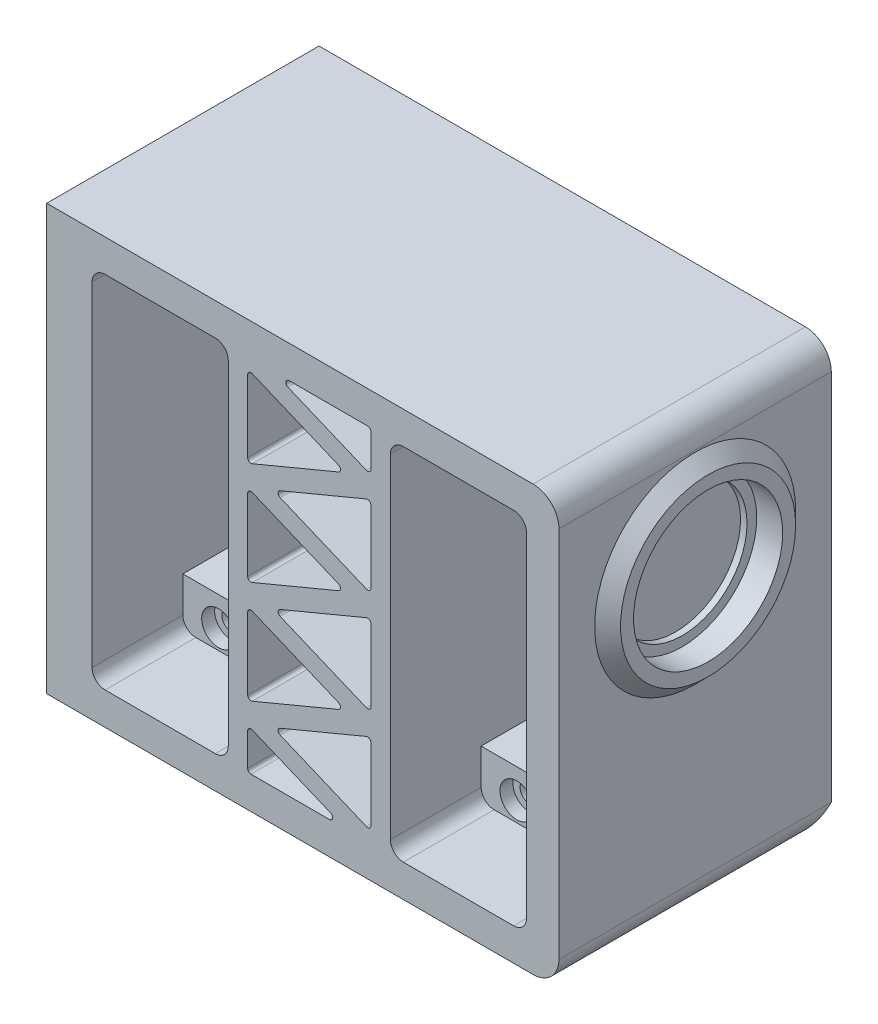
SolidWorks part; units mm, degrees
ref_plane "Front Plane" through (0, 0, 0) normal (0, 0, 1) x (1, 0, 0)
ref_plane "Top Plane" through (0, 0, 0) normal (0, 1, 0) x (1, 0, 0)
ref_plane "Right Plane" through (0, 0, 0) normal (1, 0, 0) x (0, 0, -1)
sketch "Sketch1" plane through (0, 0, 0) normal (0, 0, 1) x (1, 0, 0)
  line L0 (5, 60.5) -> (26, 60.5)
  line L1 (0, 0) -> (77, 0)
  line L2 (0, 0) -> (0, 65.5)
  line L3 (0, 65.5) -> (77, 65.5)
  line L4 (77, 0) -> (77, 65.5)
  line L5 (51, 60.5) -> (72, 60.5)
  line L6 (51, 60.5) -> (51, 5)
  line L7 (51, 5) -> (72, 5)
  line L8 (72, 60.5) -> (72, 5)
  line L9 (5, 60.5) -> (5, 5)
  line L10 (5, 5) -> (26, 5)
  line L12 (26, 60.5) -> (26, 5)
  line L13 (5, 53) -> (26, 53)
  line L14 (51, 53) -> (72, 53)
  line L15 (5, 12.5) -> (26, 12.5)
  line L16 (51, 12.5) -> (72, 12.5)
  line L17 (10.5, 57.5) -> (20.5, 57.5) construction
  line L18 (10.5, 8) -> (20.5, 8) construction
  line L19 (15.5, 57.5) -> (15.5, 8) construction
  line L20 (5, 32.75) -> (26, 32.75) construction
  line L21 (51, 32.75) -> (72, 32.75) construction
  line L22 (61.5, 57.5) -> (61.5, 8) construction
  line L23 (56.5, 57.5) -> (66.5, 57.5) construction
  line L24 (56.5, 8) -> (66.5, 8) construction
  circle A0 centre (10.5, 57.5) radius 1.5
  circle A1 centre (20.5, 57.5) radius 1.5
  circle A2 centre (10.5, 8) radius 1.5
  circle A3 centre (20.5, 8) radius 1.5
  circle A4 centre (56.5, 57.5) radius 1.5
  circle A5 centre (66.5, 57.5) radius 1.5
  circle A6 centre (66.5, 8) radius 1.5
  circle A7 centre (56.5, 8) radius 1.5
  point P33 (15.5, 32.75)
  point P34 (15.5, 32.75)
  point P41 (61.5, 32.75)
  point P42 (61.5, 32.75)
  point P53 (61.5, 8)
  point P55 (61.5, 57.5)
  dimension "D13" = 3
  dimension "D1" = 21
  dimension "D2" = 5
  dimension "D3" = 55.5
  dimension "D4" = 55.5
  dimension "D5" = 21
  dimension "D6" = 5
  dimension "D7" = 5
  dimension "D8" = 25
  dimension "D9" = 5
  dimension "D10" = 7.5
  dimension "D11" = 7.5
  dimension "D12" = 10
  dimension "D15" = 49.5
extrude "Boss-Extrude2" add sketch "Sketch1" against normal blind 28 contours L1 L4 L3 L2 L5 L8 L7 L6 L0 L12 L10 L9 | L9 L13 L12 L0 | L15 L9 L10 L12 | L16 L6 L7 L8 | L6 L14 L8 L5 | A0 | A1 | A4 | A5 | A6 | A7 | A3 | A2 region at (15.5, 56.676, 0) region at (15.5, 8.824, 0) region at (38.5, 32.75, 0) region at (61.5, 56.676, 0) region at (61.5, 8.824, 0) region at (10.5, 57.5, 0) region at (20.5, 57.5, 0) region at (56.5, 57.5, 0) region at (66.5, 57.5, 0) region at (66.5, 8, 0) region at (56.5, 8, 0)
extrude "Boss-Extrude4" add sketch "Sketch1<4>" along normal blind 14 contours L1 L4 L3 L2 L5 L8 L7 L6 L0 L12 L10 L9 region at (38.5, 32.75, 0)
sketch "Sketch1<4>" plane through (0, 0, 0) normal (0, 0, 1) x (1, 0, 0) same geometry as "Sketch1"
extrude "Cut-Extrude1" cut sketch "Sketch1<5>" against normal blind 12 contours A0 | A2 | A3 | A7 | A6 | A4 | A1 | A5 region at (10.5, 57.5, 0) region at (10.5, 8, 0) region at (20.5, 8, 0) region at (56.5, 57.5, 0) region at (66.5, 8, 0) region at (56.5, 8, 0)
sketch "Sketch1<5>" plane through (0, 0, 0) normal (0, 0, 1) x (1, 0, 0) same geometry as "Sketch1"
sketch "Sketch5" plane through (0, 0, 14) normal (0, 0, 1) x (1, 0, 0)
  line L0 (28.4223, 59.1157) -> (44.105, 52.5714)
  line L1 (26, 5) -> (51, 5)
  line L2 (26, 5) -> (26, 60.5)
  line L3 (26, 60.5) -> (51, 60.5)
  line L4 (51, 5) -> (51, 60.5)
  line L5 (26, 60.5) -> (26, 5) construction
  line L6 (51, 60.5) -> (51, 5) construction
  line L7 (5, 60.5) -> (26, 60.5) construction
  line L8 (5, 5) -> (26, 5) construction
  line L9 (29, 60.5) -> (48, 60.5)
  line L10 (48, 5) -> (48, 60.5)
  line L11 (29, 5) -> (48, 5)
  line L12 (29, 5) -> (29, 60.5)
  line L13 (29, 60.5) -> (48, 52.5714)
  line L14 (48, 52.5714) -> (29, 44.6429)
  line L15 (29, 44.6429) -> (48, 36.7143)
  line L16 (48, 36.7143) -> (29, 28.7857)
  line L17 (29, 28.7857) -> (48, 20.8571)
  line L18 (48, 20.8571) -> (29, 12.9286)
  line L19 (29, 12.9286) -> (48, 5)
  line L20 (44.105, 52.5714) -> (25.105, 44.6429)
  line L21 (25.105, 44.6429) -> (44.105, 36.7143)
  line L22 (44.105, 36.7143) -> (25.105, 28.7857)
  line L23 (25.105, 28.7857) -> (44.105, 20.8571)
  line L24 (44.105, 20.8571) -> (25.105, 12.9286)
  line L25 (25.105, 12.9286) -> (47.4223, 3.6157)
  line L26 (29.5777, 61.8843) -> (51.895, 52.5714)
  line L27 (51.895, 52.5714) -> (32.895, 44.6429)
  line L28 (32.895, 44.6429) -> (51.895, 36.7143)
  line L29 (51.895, 36.7143) -> (32.895, 28.7857)
  line L30 (32.895, 28.7857) -> (51.895, 20.8571)
  line L31 (51.895, 20.8571) -> (32.895, 12.9286)
  line L32 (32.895, 12.9286) -> (48.5777, 6.3843)
  dimension "D2" = 1.5
  dimension "D1" = 3
  dimension "D4" = 3
  dimension "D3" = 1.5
extrude "Cut-Extrude2" cut sketch "Sketch5" against normal through all contours L20 L0 L12 | L9 L26 L10 | L27 L28 L10 | L22 L21 L12 | L29 L30 L10 | L24 L23 L12 | L31 L32 L10 | L25 L12 L11 region at (34.035, 52.5714, 14) region at (42.965, 58.3989, 14) region at (34.035, 36.7143, 14) region at (42.965, 44.6429, 14) region at (42.965, 28.7857, 14) region at (34.035, 20.8571, 14) region at (42.965, 12.9286, 14) region at (34.035, 7.1011, 14)
fillet "Fillet4" radius 0.5 24 edges at (44.105, 5, -7) (29, 11.3032, -7) (29, 5, -7) (48, 6.6254, -7) (48, 19.2318, -7) (32.895, 12.9286, -7) (29, 14.5539, -7) (29, 27.1604, -7) (44.105, 20.8571, -7) (48, 22.4825, -7) (48, 35.0889, -7) (32.895, 28.7857, -7) (44.105, 36.7143, -7) (29, 30.4111, -7) (29, 43.0175, -7) (48, 38.3396, -7) (32.895, 44.6429, -7) (48, 50.9461, -7) (29, 46.2682, -7) (44.105, 52.5714, -7) (29, 58.8746, -7) (48, 54.1968, -7) (48, 60.5, -7) (32.895, 60.5, -7)
sketch "Sketch8" plane through (0, 12.5, 0) normal (0, 1, 0) x (1, 0, 0)
  line L0 (26, 28) -> (26, 0) construction
  line L1 (5, 28) -> (26, 28)
  line L2 (5, 28) -> (5, 8)
  line L3 (5, 8) -> (26, 8)
  line L4 (26, 28) -> (26, 8)
  line L5 (51, 0) -> (72, 0) construction
  line L6 (51, 28) -> (72, 28)
  line L7 (51, 28) -> (51, 8)
  line L8 (51, 8) -> (72, 8)
  line L9 (72, 28) -> (72, 8)
  line L10 (72, 28) -> (72, 0) construction
  dimension "D1" = 8
extrude "Cut-Extrude8" cut sketch "Sketch8" against normal blind 10
ref_plane "Midplane" through (0, 32.75, 0) normal (0, 1, 0) x (1, 0, 0)
ref_plane "Plane2" through (61.5, 0, 0) normal (1, 0, 0) x (0, 0, -1)
ref_plane "Plane3" through (15.5, 0, 0) normal (1, 0, 0) x (0, 0, -1)
sketch "Sketch10" plane through (61.5, 0, 0) normal (1, 0, 0) x (0, 0, -1)
  line L0 (28, 2.5) -> (8, 2.5) construction
  line L1 (8, 2.5) -> (8, 12.5) construction
  line L2 (28, 2.5) -> (8, 2.5)
  line L3 (8, 2.5) -> (8, 12.5)
  line L4 (8, 12.5) -> (18, 2.5)
  dimension "D1" = 45
extrude "Boss-Extrude5" add sketch "Sketch10" along normal blind 1.5 and the other way blind 1.5 contours L4 L3 L2 region at (61.5, 5.8333, -11.3333)
sketch "Sketch11" plane through (15.5, 0, 0) normal (1, 0, 0) x (0, 0, -1)
  line L0 (28, 2.5) -> (8, 2.5) construction
  line L1 (8, 2.5) -> (8, 12.5) construction
  line L2 (28, 2.5) -> (8, 2.5)
  line L3 (8, 2.5) -> (8, 12.5)
  line L4 (8, 12.5) -> (18, 2.5)
  dimension "D1" = 45
extrude "Boss-Extrude6" add sketch "Sketch11" along normal blind 1.5 and the other way blind 1.5 contours L4 L3 L2 region at (15.5, 5.8333, -11.3333)
mirror "Mirror2" about plane through (0, 32.75, 0) normal (0, 1, 0) of "Boss-Extrude6", "Boss-Extrude5", "Cut-Extrude8"
sketch "Sketch13" plane through (0, 0, 0) normal (-1, 0, 0) x (0, 0, 1)
  line L4 (-28, 0) -> (14, 0)
  line L5 (14, 0) -> (14, 65.5)
  line L6 (14, 65.5) -> (-28, 65.5)
  line L7 (-28, 65.5) -> (-28, 0)
  line L8 (-28, 0) -> (14, 0)
  line L9 (14, 0) -> (14, 65.5)
  line L10 (14, 65.5) -> (-28, 65.5)
  line L11 (-28, 65.5) -> (-28, 0)
  dimension "D1" = 0
extrude "Boss-Extrude7" add sketch "Sketch13" along normal blind 2
fillet "Fillet3" radius 2 16 edges at (51, 60.5, 7) (72, 5, 7) (72, 60.5, 7) (51, 5, 7) (5, 5, 7) (26, 5, 7) (26, 60.5, 7) (5, 60.5, 7) (72, 63, -18) (72, 2.5, -18) (51, 2.5, -18) (51, 63, -18) (26, 63, -18) (26, 2.5, -18) (5, 63, -18) (5, 2.5, -18)
sketch "Sketch14" plane through (-2, 0, 0) normal (-1, 0, 0) x (0, 0, 1)
  line L8 (-24, 61.5) -> (-24, 4)
  line L9 (-24, 4) -> (10, 4)
  line L10 (10, 4) -> (10, 61.5)
  line L11 (10, 61.5) -> (-24, 61.5)
  line L12 (-24, 61.5) -> (-24, 4) construction
  line L13 (-24, 4) -> (10, 4) construction
  line L14 (10, 4) -> (10, 61.5) construction
  line L15 (10, 61.5) -> (-24, 61.5) construction
  circle A0 centre (-24, 61.5) radius 1.25
  circle A1 centre (10, 61.5) radius 1.25
  circle A2 centre (10, 4) radius 1.25
  circle A3 centre (-24, 4) radius 1.25
  dimension "D2" = 2.5
  dimension "D1" = 4
extrude "Cut-Extrude9" cut sketch "Sketch14" against normal blind 7
fillet "Fillet7" radius 4 2 edges at (77, 65.5, -7) (77, 0, -7)
sketch "Sketch15" plane through (77, 0, 0) normal (1, 0, 0) x (0, 0, -1)
  line L0 (-14, 32.75) -> (28, 32.75) construction
  line L1 (-14, 4) -> (-14, 61.5) construction
  line L2 (28, 4) -> (28, 61.5) construction
  line L3 (-14, 45.75) -> (28, 45.75) construction
  circle A0 centre (7, 45.75) radius 13.5
  dimension "D2" = 27
  dimension "D1" = 13
extrude "Boss-Extrude8" add sketch "Sketch15" along normal blind 2
sketch "Sketch16" plane through (79, 0, 0) normal (1, 0, 0) x (0, 0, -1)
  circle A0 centre (7, 45.75) radius 11.5
  dimension "D1" = 23
extrude "Cut-Extrude10" cut sketch "Sketch16" against normal blind 4
chamfer "Chamfer1" distance 2 angle 45 1 edges at (77, 45.75, -20.5)
sketch "Sketch17" plane through (75, 0, 0) normal (1, 0, 0) x (0, 0, -1)
  circle A0 centre (7, 45.75) radius 10
  dimension "D1" = 20
extrude "Cut-Extrude11" cut sketch "Sketch17" against normal blind 1
sketch "Sketch18" plane through (0, 0, 0) normal (0, 0, 1) x (1, 0, 0)
  circle A0 centre (10.5, 57.5) radius 2.6
  circle A1 centre (20.5, 57.5) radius 2.6
  circle A2 centre (56.5, 57.5) radius 2.6
  circle A3 centre (66.5, 57.5) radius 2.6
  circle A4 centre (66.5, 8) radius 2.6
  circle A5 centre (56.5, 8) radius 2.6
  circle A6 centre (20.5, 8) radius 2.6
  circle A7 centre (10.5, 8) radius 2.6
  dimension "D1" = 5.2
extrude "Cut-Extrude12" cut sketch "Sketch18" against normal blind 2
sketch "Sketch19" plane through (-2, 0, 0) normal (-1, 0, 0) x (0, 0, 1)
  line L0 (-28, 4) -> (-24, 0)
  line L1 (-28, 65.5) -> (-28, 0) construction
  line L2 (-28, 0) -> (14, 0) construction
  line L3 (-28, 4) -> (-28, 0)
  line L4 (-28, 0) -> (-24, 0)
  dimension "D1" = 4
extrude "Cut-Extrude13" cut sketch "Sketch19" against normal through all
